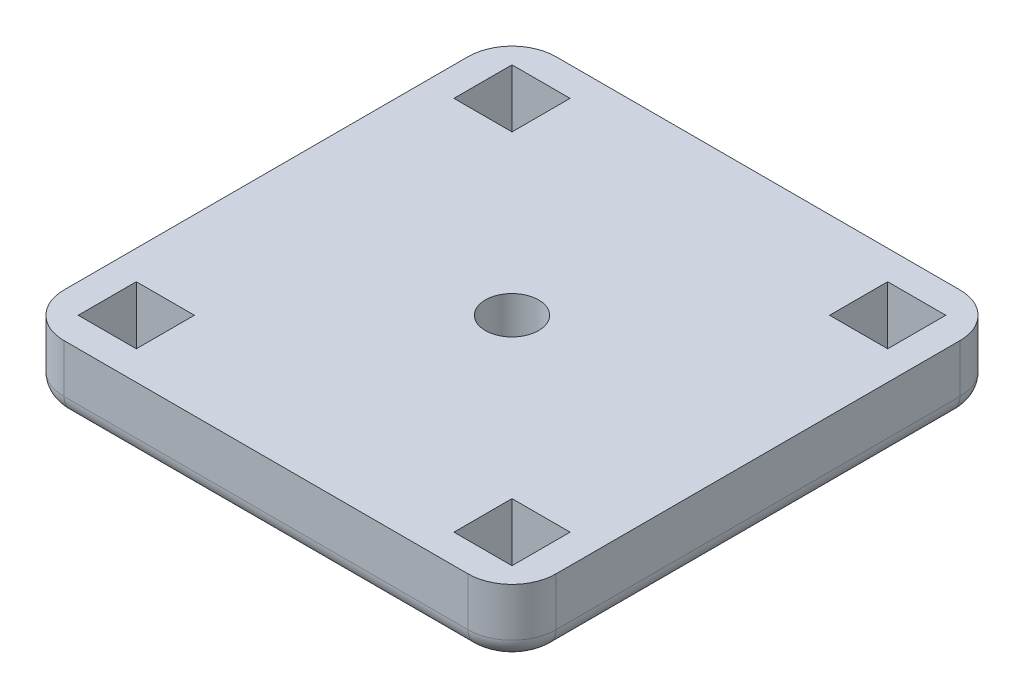
SolidWorks part; units mm, degrees
ref_plane "Front Plane" through (0, 0, 0) normal (0, 0, 1) x (1, 0, 0)
ref_plane "Top Plane" through (0, 0, 0) normal (0, 1, 0) x (1, 0, 0)
ref_plane "Right Plane" through (0, 0, 0) normal (1, 0, 0) x (0, 0, -1)
sketch "Sketch1" plane through (0, 0, 0) normal (0, 1, 0) x (1, 0, 0)
  line L0 (0, 40.9558) -> (0, -31.5279) construction
  line L1 (-25.4, 25.4) -> (25.4, 25.4)
  line L2 (-25.4, 25.4) -> (-25.4, -25.4)
  line L3 (-25.4, -25.4) -> (25.4, -25.4)
  line L4 (25.4, 25.4) -> (25.4, -25.4)
  line L5 (-25.4, 25.4) -> (25.4, -25.4) construction
  line L6 (-25.4, -25.4) -> (25.4, 25.4) construction
  line L7 (-16.4, 16.4) -> (-22.4, 16.4)
  line L8 (-16.4, 16.4) -> (-16.4, 22.4)
  line L9 (-16.4, 22.4) -> (-22.4, 22.4)
  line L10 (-22.4, 16.4) -> (-22.4, 22.4)
  line L11 (-16.4, 16.4) -> (-22.4, 22.4) construction
  line L12 (-16.4, 22.4) -> (-22.4, 16.4) construction
  line L13 (39.9537, 0) -> (-38.7868, 0) construction
  line L14 (16.4, 16.4) -> (22.4, 16.4)
  line L15 (16.4, 22.4) -> (22.4, 16.4) construction
  line L16 (16.4, 16.4) -> (22.4, 22.4) construction
  line L17 (25.4, 25.4) -> (-25.4, -25.4) construction
  line L18 (22.4, 16.4) -> (22.4, 22.4)
  line L19 (16.4, 22.4) -> (22.4, 22.4)
  line L20 (16.4, 16.4) -> (16.4, 22.4)
  line L21 (-22.4, -16.4) -> (-22.4, -22.4)
  line L22 (16.4, -22.4) -> (22.4, -22.4)
  line L23 (-16.4, -22.4) -> (-22.4, -22.4)
  line L24 (25.4, -25.4) -> (-25.4, 25.4) construction
  line L25 (16.4, -16.4) -> (22.4, -22.4) construction
  line L26 (16.4, -22.4) -> (22.4, -16.4) construction
  line L27 (-16.4, -22.4) -> (-22.4, -16.4) construction
  line L28 (-16.4, -16.4) -> (-22.4, -22.4) construction
  line L29 (-25.4, 25.4) -> (25.4, -25.4) construction
  line L30 (-25.4, -25.4) -> (25.4, 25.4) construction
  line L31 (0, -40.9558) -> (0, 31.5279) construction
  line L32 (16.4, -16.4) -> (16.4, -22.4)
  line L33 (22.4, -16.4) -> (22.4, -22.4)
  line L34 (16.4, -16.4) -> (22.4, -16.4)
  line L35 (-16.4, -16.4) -> (-16.4, -22.4)
  line L36 (-16.4, -16.4) -> (-22.4, -16.4)
  circle A0 centre (0, 0) radius 2.75
  point P0 (0, 0)
  point P8 (-19.4, 19.4)
  point P21 (19.4, 19.4)
  point P32 (19.4, -19.4)
  point P33 (-19.4, -19.4)
  dimension "D3" = 5.5
  dimension "D1" = 50.8
  dimension "D2" = 50.8
  dimension "D4" = 6
  dimension "D5" = 3
extrude "Boss-Extrude1" add sketch "Sketch1" along normal blind 7
fillet "Fillet1" radius 2 4 edges at (-25.4, 0, 0) (0, 0, -25.4) (0, 0, 25.4) (25.4, 0, 0)
fillet "Fillet2" radius 4.54 8 edges at (24.8142, 0.5858, -24.8142) (24.8142, 0.5858, 24.8142) (-24.8142, 0.5858, -24.8142) (-24.8142, 0.5858, 24.8142) (-25.4, 4.5, 25.4) (-25.4, 4.5, -25.4) (25.4, 4.5, 25.4) (25.4, 4.5, -25.4)
